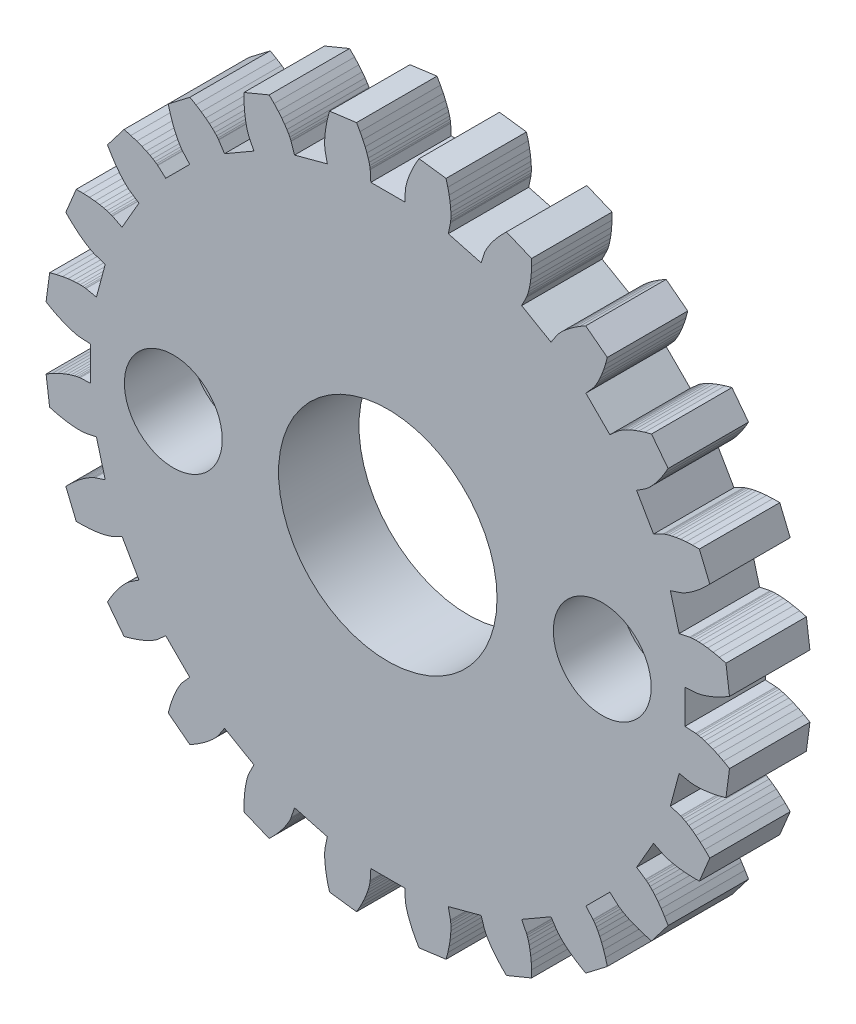
SolidWorks part; units mm, degrees
material "ABS"
ref_plane "Front Plane" through (0, 0, 0) normal (0, 0, 1) x (1, 0, 0)
ref_plane "Top Plane" through (0, 0, 0) normal (0, 1, 0) x (1, 0, 0)
ref_plane "Right Plane" through (0, 0, 0) normal (1, 0, 0) x (0, 0, -1)
sketch "Model" plane through (0, 0, 0) normal (0, 0, 1) x (1, 0, 0)
  line L0 (11.4813, -0.6559) -> (11.0819, -0.6331)
  line L1 (11.0819, -0.6331) -> (11.0819, 0.6331)
  line L2 (11.4813, 0.6559) -> (11.0819, 0.6331)
  line L3 (11.4813, 0.6559) -> (11.495, 0.6571)
  line L4 (11.495, 0.6571) -> (11.5358, 0.6626)
  line L5 (11.5358, 0.6626) -> (11.6033, 0.6749)
  line L6 (11.6033, 0.6749) -> (11.697, 0.6968)
  line L7 (11.697, 0.6968) -> (11.8158, 0.7307)
  line L8 (11.8158, 0.7307) -> (11.9589, 0.7792)
  line L9 (11.9589, 0.7792) -> (12.125, 0.8446)
  line L10 (12.125, 0.8446) -> (12.3128, 0.9294)
  line L11 (12.3128, 0.9294) -> (12.5206, 1.0358)
  line L12 (12.5206, 1.0358) -> (12.7468, 1.1658)
  line L13 (11.2598, 2.338) -> (11.2734, 2.3404)
  line L14 (11.2734, 2.3404) -> (11.3142, 2.3457)
  line L15 (11.3142, 2.3457) -> (11.3827, 2.3512)
  line L16 (11.3827, 2.3512) -> (11.4787, 2.3543)
  line L17 (11.4787, 2.3543) -> (11.6023, 2.3524)
  line L18 (11.6023, 2.3524) -> (11.7531, 2.3426)
  line L19 (11.7531, 2.3426) -> (11.9305, 2.3223)
  line L20 (11.9305, 2.3223) -> (12.1338, 2.289)
  line L21 (12.1338, 2.289) -> (12.362, 2.2401)
  line L22 (12.362, 2.2401) -> (12.6142, 2.173)
  line L23 (12.7468, 1.1658) -> (12.6142, 2.173)
  line L24 (11.2598, 2.338) -> (10.8682, 2.2567)
  line L25 (10.8682, 2.2567) -> (10.5405, 3.4797)
  line L26 (10.9203, 3.6051) -> (10.5405, 3.4797)
  line L27 (10.9203, 3.6051) -> (10.9332, 3.6098)
  line L28 (10.9332, 3.6098) -> (10.9712, 3.6257)
  line L29 (10.9712, 3.6257) -> (11.0333, 3.6551)
  line L30 (11.0333, 3.6551) -> (11.1181, 3.7004)
  line L31 (11.1181, 3.7004) -> (11.2241, 3.764)
  line L32 (11.2241, 3.764) -> (11.3497, 3.8478)
  line L33 (11.3497, 3.8478) -> (11.4933, 3.954)
  line L34 (11.4933, 3.954) -> (11.6527, 4.0845)
  line L35 (11.6527, 4.0845) -> (11.8259, 4.241)
  line L36 (11.8259, 4.241) -> (12.0107, 4.4252)
  line L37 (10.271, 5.1726) -> (10.2835, 5.1784)
  line L38 (10.2835, 5.1784) -> (10.3216, 5.1941)
  line L39 (10.3216, 5.1941) -> (10.3863, 5.2172)
  line L40 (10.3863, 5.2172) -> (10.4783, 5.245)
  line L41 (10.4783, 5.245) -> (10.5981, 5.2751)
  line L42 (10.5981, 5.2751) -> (10.7463, 5.3047)
  line L43 (10.7463, 5.3047) -> (10.9229, 5.331)
  line L44 (10.9229, 5.331) -> (11.1279, 5.3515)
  line L45 (11.1279, 5.3515) -> (11.361, 5.3633)
  line L46 (11.361, 5.3633) -> (11.622, 5.3638)
  line L47 (12.0107, 4.4252) -> (11.622, 5.3638)
  line L48 (10.271, 5.1726) -> (9.9138, 4.9927)
  line L49 (9.9138, 4.9927) -> (9.2807, 6.0892)
  line L50 (9.6151, 6.3087) -> (9.2807, 6.0892)
  line L51 (9.6151, 6.3087) -> (9.6264, 6.3166)
  line L52 (9.6264, 6.3166) -> (9.659, 6.3417)
  line L53 (9.659, 6.3417) -> (9.7113, 6.3862)
  line L54 (9.7113, 6.3862) -> (9.7815, 6.4519)
  line L55 (9.7815, 6.4519) -> (9.8675, 6.5407)
  line L56 (9.8675, 6.5407) -> (9.9671, 6.6542)
  line L57 (9.9671, 6.6542) -> (10.0783, 6.794)
  line L58 (10.0783, 6.794) -> (10.1985, 6.9613)
  line L59 (10.1985, 6.9613) -> (10.3253, 7.1573)
  line L60 (10.3253, 7.1573) -> (10.4561, 7.383)
  line L61 (8.5823, 7.6547) -> (8.5928, 7.6635)
  line L62 (8.5928, 7.6635) -> (8.6256, 7.6885)
  line L63 (8.6256, 7.6885) -> (8.6821, 7.7275)
  line L64 (8.6821, 7.7275) -> (8.7637, 7.7783)
  line L65 (8.7637, 7.7783) -> (8.8717, 7.8384)
  line L66 (8.8717, 7.8384) -> (9.0072, 7.9053)
  line L67 (9.0072, 7.9053) -> (9.1709, 7.9764)
  line L68 (9.1709, 7.9764) -> (9.3636, 8.0492)
  line L69 (9.3636, 8.0492) -> (9.5858, 8.121)
  line L70 (9.5858, 8.121) -> (9.8377, 8.189)
  line L71 (10.4561, 7.383) -> (9.8377, 8.189)
  line L72 (8.5823, 7.6547) -> (8.2838, 7.3885)
  line L73 (8.2838, 7.3885) -> (7.3885, 8.2838)
  line L74 (7.6547, 8.5823) -> (7.3885, 8.2838)
  line L75 (7.6547, 8.5823) -> (7.6635, 8.5928)
  line L76 (7.6635, 8.5928) -> (7.6885, 8.6256)
  line L77 (7.6885, 8.6256) -> (7.7275, 8.6821)
  line L78 (7.7275, 8.6821) -> (7.7783, 8.7637)
  line L79 (7.7783, 8.7637) -> (7.8384, 8.8717)
  line L80 (7.8384, 8.8717) -> (7.9053, 9.0072)
  line L81 (7.9053, 9.0072) -> (7.9764, 9.1709)
  line L82 (7.9764, 9.1709) -> (8.0492, 9.3636)
  line L83 (8.0492, 9.3636) -> (8.121, 9.5858)
  line L84 (8.121, 9.5858) -> (8.189, 9.8377)
  line L85 (6.3087, 9.6151) -> (6.3166, 9.6264)
  line L86 (6.3166, 9.6264) -> (6.3417, 9.659)
  line L87 (6.3417, 9.659) -> (6.3862, 9.7113)
  line L88 (6.3862, 9.7113) -> (6.4519, 9.7815)
  line L89 (6.4519, 9.7815) -> (6.5407, 9.8675)
  line L90 (6.5407, 9.8675) -> (6.6542, 9.9671)
  line L91 (6.6542, 9.9671) -> (6.794, 10.0783)
  line L92 (6.794, 10.0783) -> (6.9613, 10.1985)
  line L93 (6.9613, 10.1985) -> (7.1573, 10.3253)
  line L94 (7.1573, 10.3253) -> (7.383, 10.4561)
  line L95 (8.189, 9.8377) -> (7.383, 10.4561)
  line L96 (6.3087, 9.6151) -> (6.0892, 9.2807)
  line L97 (6.0892, 9.2807) -> (4.9927, 9.9138)
  line L98 (5.1726, 10.271) -> (4.9927, 9.9138)
  line L99 (5.1726, 10.271) -> (5.1784, 10.2835)
  line L100 (5.1784, 10.2835) -> (5.1941, 10.3216)
  line L101 (5.1941, 10.3216) -> (5.2172, 10.3863)
  line L102 (5.2172, 10.3863) -> (5.245, 10.4783)
  line L103 (5.245, 10.4783) -> (5.2751, 10.5981)
  line L104 (5.2751, 10.5981) -> (5.3047, 10.7463)
  line L105 (5.3047, 10.7463) -> (5.331, 10.9229)
  line L106 (5.331, 10.9229) -> (5.3515, 11.1279)
  line L107 (5.3515, 11.1279) -> (5.3633, 11.361)
  line L108 (5.3633, 11.361) -> (5.3638, 11.622)
  line L109 (3.6051, 10.9203) -> (3.6098, 10.9332)
  line L110 (3.6098, 10.9332) -> (3.6257, 10.9712)
  line L111 (3.6257, 10.9712) -> (3.6551, 11.0333)
  line L112 (3.6551, 11.0333) -> (3.7004, 11.1181)
  line L113 (3.7004, 11.1181) -> (3.764, 11.2241)
  line L114 (3.764, 11.2241) -> (3.8478, 11.3497)
  line L115 (3.8478, 11.3497) -> (3.954, 11.4933)
  line L116 (3.954, 11.4933) -> (4.0845, 11.6527)
  line L117 (4.0845, 11.6527) -> (4.241, 11.8259)
  line L118 (4.241, 11.8259) -> (4.4252, 12.0107)
  line L119 (5.3638, 11.622) -> (4.4252, 12.0107)
  line L120 (3.6051, 10.9203) -> (3.4797, 10.5405)
  line L121 (3.4797, 10.5405) -> (2.2567, 10.8682)
  line L122 (2.338, 11.2598) -> (2.2567, 10.8682)
  line L123 (2.338, 11.2598) -> (2.3404, 11.2734)
  line L124 (2.3404, 11.2734) -> (2.3457, 11.3142)
  line L125 (2.3457, 11.3142) -> (2.3512, 11.3827)
  line L126 (2.3512, 11.3827) -> (2.3543, 11.4787)
  line L127 (2.3543, 11.4787) -> (2.3524, 11.6023)
  line L128 (2.3524, 11.6023) -> (2.3426, 11.7531)
  line L129 (2.3426, 11.7531) -> (2.3223, 11.9305)
  line L130 (2.3223, 11.9305) -> (2.289, 12.1338)
  line L131 (2.289, 12.1338) -> (2.2401, 12.362)
  line L132 (2.2401, 12.362) -> (2.173, 12.6142)
  line L133 (0.6559, 11.4813) -> (0.6571, 11.495)
  line L134 (0.6571, 11.495) -> (0.6626, 11.5358)
  line L135 (0.6626, 11.5358) -> (0.6749, 11.6033)
  line L136 (0.6749, 11.6033) -> (0.6968, 11.697)
  line L137 (0.6968, 11.697) -> (0.7307, 11.8158)
  line L138 (0.7307, 11.8158) -> (0.7792, 11.9589)
  line L139 (0.7792, 11.9589) -> (0.8446, 12.125)
  line L140 (0.8446, 12.125) -> (0.9294, 12.3128)
  line L141 (0.9294, 12.3128) -> (1.0358, 12.5206)
  line L142 (1.0358, 12.5206) -> (1.1658, 12.7468)
  line L143 (2.173, 12.6142) -> (1.1658, 12.7468)
  line L144 (0.6559, 11.4813) -> (0.6331, 11.0819)
  line L145 (0.6331, 11.0819) -> (-0.6331, 11.0819)
  line L146 (-0.6559, 11.4813) -> (-0.6331, 11.0819)
  line L147 (-0.6559, 11.4813) -> (-0.6571, 11.495)
  line L148 (-0.6571, 11.495) -> (-0.6626, 11.5358)
  line L149 (-0.6626, 11.5358) -> (-0.6749, 11.6033)
  line L150 (-0.6749, 11.6033) -> (-0.6968, 11.697)
  line L151 (-0.6968, 11.697) -> (-0.7307, 11.8158)
  line L152 (-0.7307, 11.8158) -> (-0.7792, 11.9589)
  line L153 (-0.7792, 11.9589) -> (-0.8446, 12.125)
  line L154 (-0.8446, 12.125) -> (-0.9294, 12.3128)
  line L155 (-0.9294, 12.3128) -> (-1.0358, 12.5206)
  line L156 (-1.0358, 12.5206) -> (-1.1658, 12.7468)
  line L157 (-2.338, 11.2598) -> (-2.3404, 11.2734)
  line L158 (-2.3404, 11.2734) -> (-2.3457, 11.3142)
  line L159 (-2.3457, 11.3142) -> (-2.3512, 11.3827)
  line L160 (-2.3512, 11.3827) -> (-2.3543, 11.4787)
  line L161 (-2.3543, 11.4787) -> (-2.3524, 11.6023)
  line L162 (-2.3524, 11.6023) -> (-2.3426, 11.7531)
  line L163 (-2.3426, 11.7531) -> (-2.3223, 11.9305)
  line L164 (-2.3223, 11.9305) -> (-2.289, 12.1338)
  line L165 (-2.289, 12.1338) -> (-2.2401, 12.362)
  line L166 (-2.2401, 12.362) -> (-2.173, 12.6142)
  line L167 (-1.1658, 12.7468) -> (-2.173, 12.6142)
  line L168 (-2.338, 11.2598) -> (-2.2567, 10.8682)
  line L169 (-2.2567, 10.8682) -> (-3.4797, 10.5405)
  line L170 (-3.6051, 10.9203) -> (-3.4797, 10.5405)
  line L171 (-3.6051, 10.9203) -> (-3.6098, 10.9332)
  line L172 (-3.6098, 10.9332) -> (-3.6257, 10.9712)
  line L173 (-3.6257, 10.9712) -> (-3.6551, 11.0333)
  line L174 (-3.6551, 11.0333) -> (-3.7004, 11.1181)
  line L175 (-3.7004, 11.1181) -> (-3.764, 11.2241)
  line L176 (-3.764, 11.2241) -> (-3.8478, 11.3497)
  line L177 (-3.8478, 11.3497) -> (-3.954, 11.4933)
  line L178 (-3.954, 11.4933) -> (-4.0845, 11.6527)
  line L179 (-4.0845, 11.6527) -> (-4.241, 11.8259)
  line L180 (-4.241, 11.8259) -> (-4.4252, 12.0107)
  line L181 (-5.1726, 10.271) -> (-5.1784, 10.2835)
  line L182 (-5.1784, 10.2835) -> (-5.1941, 10.3216)
  line L183 (-5.1941, 10.3216) -> (-5.2172, 10.3863)
  line L184 (-5.2172, 10.3863) -> (-5.245, 10.4783)
  line L185 (-5.245, 10.4783) -> (-5.2751, 10.5981)
  line L186 (-5.2751, 10.5981) -> (-5.3047, 10.7463)
  line L187 (-5.3047, 10.7463) -> (-5.331, 10.9229)
  line L188 (-5.331, 10.9229) -> (-5.3515, 11.1279)
  line L189 (-5.3515, 11.1279) -> (-5.3633, 11.361)
  line L190 (-5.3633, 11.361) -> (-5.3638, 11.622)
  line L191 (-4.4252, 12.0107) -> (-5.3638, 11.622)
  line L192 (-5.1726, 10.271) -> (-4.9927, 9.9138)
  line L193 (-4.9927, 9.9138) -> (-6.0892, 9.2807)
  line L194 (-6.3087, 9.6151) -> (-6.0892, 9.2807)
  line L195 (-6.3087, 9.6151) -> (-6.3166, 9.6264)
  line L196 (-6.3166, 9.6264) -> (-6.3417, 9.659)
  line L197 (-6.3417, 9.659) -> (-6.3862, 9.7113)
  line L198 (-6.3862, 9.7113) -> (-6.4519, 9.7815)
  line L199 (-6.4519, 9.7815) -> (-6.5407, 9.8675)
  line L200 (-6.5407, 9.8675) -> (-6.6542, 9.9671)
  line L201 (-6.6542, 9.9671) -> (-6.794, 10.0783)
  line L202 (-6.794, 10.0783) -> (-6.9613, 10.1985)
  line L203 (-6.9613, 10.1985) -> (-7.1573, 10.3253)
  line L204 (-7.1573, 10.3253) -> (-7.383, 10.4561)
  line L205 (-7.6547, 8.5823) -> (-7.6635, 8.5928)
  line L206 (-7.6635, 8.5928) -> (-7.6885, 8.6256)
  line L207 (-7.6885, 8.6256) -> (-7.7275, 8.6821)
  line L208 (-7.7275, 8.6821) -> (-7.7783, 8.7637)
  line L209 (-7.7783, 8.7637) -> (-7.8384, 8.8717)
  line L210 (-7.8384, 8.8717) -> (-7.9053, 9.0072)
  line L211 (-7.9053, 9.0072) -> (-7.9764, 9.1709)
  line L212 (-7.9764, 9.1709) -> (-8.0492, 9.3636)
  line L213 (-8.0492, 9.3636) -> (-8.121, 9.5858)
  line L214 (-8.121, 9.5858) -> (-8.189, 9.8377)
  line L215 (-7.383, 10.4561) -> (-8.189, 9.8377)
  line L216 (-7.6547, 8.5823) -> (-7.3885, 8.2838)
  line L217 (-7.3885, 8.2838) -> (-8.2838, 7.3885)
  line L218 (-8.5823, 7.6547) -> (-8.2838, 7.3885)
  line L219 (-8.5823, 7.6547) -> (-8.5928, 7.6635)
  line L220 (-8.5928, 7.6635) -> (-8.6256, 7.6885)
  line L221 (-8.6256, 7.6885) -> (-8.6821, 7.7275)
  line L222 (-8.6821, 7.7275) -> (-8.7637, 7.7783)
  line L223 (-8.7637, 7.7783) -> (-8.8717, 7.8384)
  line L224 (-8.8717, 7.8384) -> (-9.0072, 7.9053)
  line L225 (-9.0072, 7.9053) -> (-9.1709, 7.9764)
  line L226 (-9.1709, 7.9764) -> (-9.3636, 8.0492)
  line L227 (-9.3636, 8.0492) -> (-9.5858, 8.121)
  line L228 (-9.5858, 8.121) -> (-9.8377, 8.189)
  line L229 (-9.6151, 6.3087) -> (-9.6264, 6.3166)
  line L230 (-9.6264, 6.3166) -> (-9.659, 6.3417)
  line L231 (-9.659, 6.3417) -> (-9.7113, 6.3862)
  line L232 (-9.7113, 6.3862) -> (-9.7815, 6.4519)
  line L233 (-9.7815, 6.4519) -> (-9.8675, 6.5407)
  line L234 (-9.8675, 6.5407) -> (-9.9671, 6.6542)
  line L235 (-9.9671, 6.6542) -> (-10.0783, 6.794)
  line L236 (-10.0783, 6.794) -> (-10.1985, 6.9613)
  line L237 (-10.1985, 6.9613) -> (-10.3253, 7.1573)
  line L238 (-10.3253, 7.1573) -> (-10.4561, 7.383)
  line L239 (-9.8377, 8.189) -> (-10.4561, 7.383)
  line L240 (-9.6151, 6.3087) -> (-9.2807, 6.0892)
  line L241 (-9.2807, 6.0892) -> (-9.9138, 4.9927)
  line L242 (-10.271, 5.1726) -> (-9.9138, 4.9927)
  line L243 (-10.271, 5.1726) -> (-10.2835, 5.1784)
  line L244 (-10.2835, 5.1784) -> (-10.3216, 5.1941)
  line L245 (-10.3216, 5.1941) -> (-10.3863, 5.2172)
  line L246 (-10.3863, 5.2172) -> (-10.4783, 5.245)
  line L247 (-10.4783, 5.245) -> (-10.5981, 5.2751)
  line L248 (-10.5981, 5.2751) -> (-10.7463, 5.3047)
  line L249 (-10.7463, 5.3047) -> (-10.9229, 5.331)
  line L250 (-10.9229, 5.331) -> (-11.1279, 5.3515)
  line L251 (-11.1279, 5.3515) -> (-11.361, 5.3633)
  line L252 (-11.361, 5.3633) -> (-11.622, 5.3638)
  line L253 (-10.9203, 3.6051) -> (-10.9332, 3.6098)
  line L254 (-10.9332, 3.6098) -> (-10.9712, 3.6257)
  line L255 (-10.9712, 3.6257) -> (-11.0333, 3.6551)
  line L256 (-11.0333, 3.6551) -> (-11.1181, 3.7004)
  line L257 (-11.1181, 3.7004) -> (-11.2241, 3.764)
  line L258 (-11.2241, 3.764) -> (-11.3497, 3.8478)
  line L259 (-11.3497, 3.8478) -> (-11.4933, 3.954)
  line L260 (-11.4933, 3.954) -> (-11.6527, 4.0845)
  line L261 (-11.6527, 4.0845) -> (-11.8259, 4.241)
  line L262 (-11.8259, 4.241) -> (-12.0107, 4.4252)
  line L263 (-11.622, 5.3638) -> (-12.0107, 4.4252)
  line L264 (-10.9203, 3.6051) -> (-10.5405, 3.4797)
  line L265 (-10.5405, 3.4797) -> (-10.8682, 2.2567)
  line L266 (-11.2598, 2.338) -> (-10.8682, 2.2567)
  line L267 (-11.2598, 2.338) -> (-11.2734, 2.3404)
  line L268 (-11.2734, 2.3404) -> (-11.3142, 2.3457)
  line L269 (-11.3142, 2.3457) -> (-11.3827, 2.3512)
  line L270 (-11.3827, 2.3512) -> (-11.4787, 2.3543)
  line L271 (-11.4787, 2.3543) -> (-11.6023, 2.3524)
  line L272 (-11.6023, 2.3524) -> (-11.7531, 2.3426)
  line L273 (-11.7531, 2.3426) -> (-11.9305, 2.3223)
  line L274 (-11.9305, 2.3223) -> (-12.1338, 2.289)
  line L275 (-12.1338, 2.289) -> (-12.362, 2.2401)
  line L276 (-12.362, 2.2401) -> (-12.6142, 2.173)
  line L277 (-11.4813, 0.6559) -> (-11.495, 0.6571)
  line L278 (-11.495, 0.6571) -> (-11.5358, 0.6626)
  line L279 (-11.5358, 0.6626) -> (-11.6033, 0.6749)
  line L280 (-11.6033, 0.6749) -> (-11.697, 0.6968)
  line L281 (-11.697, 0.6968) -> (-11.8158, 0.7307)
  line L282 (-11.8158, 0.7307) -> (-11.9589, 0.7792)
  line L283 (-11.9589, 0.7792) -> (-12.125, 0.8446)
  line L284 (-12.125, 0.8446) -> (-12.3128, 0.9294)
  line L285 (-12.3128, 0.9294) -> (-12.5206, 1.0358)
  line L286 (-12.5206, 1.0358) -> (-12.7468, 1.1658)
  line L287 (-12.6142, 2.173) -> (-12.7468, 1.1658)
  line L288 (-11.4813, 0.6559) -> (-11.0819, 0.6331)
  line L289 (-11.0819, 0.6331) -> (-11.0819, -0.6331)
  line L290 (-11.4813, -0.6559) -> (-11.0819, -0.6331)
  line L291 (-11.4813, -0.6559) -> (-11.495, -0.6571)
  line L292 (-11.495, -0.6571) -> (-11.5358, -0.6626)
  line L293 (-11.5358, -0.6626) -> (-11.6033, -0.6749)
  line L294 (-11.6033, -0.6749) -> (-11.697, -0.6968)
  line L295 (-11.697, -0.6968) -> (-11.8158, -0.7307)
  line L296 (-11.8158, -0.7307) -> (-11.9589, -0.7792)
  line L297 (-11.9589, -0.7792) -> (-12.125, -0.8446)
  line L298 (-12.125, -0.8446) -> (-12.3128, -0.9294)
  line L299 (-12.3128, -0.9294) -> (-12.5206, -1.0358)
  line L300 (-12.5206, -1.0358) -> (-12.7468, -1.1658)
  line L301 (-11.2598, -2.338) -> (-11.2734, -2.3404)
  line L302 (-11.2734, -2.3404) -> (-11.3142, -2.3457)
  line L303 (-11.3142, -2.3457) -> (-11.3827, -2.3512)
  line L304 (-11.3827, -2.3512) -> (-11.4787, -2.3543)
  line L305 (-11.4787, -2.3543) -> (-11.6023, -2.3524)
  line L306 (-11.6023, -2.3524) -> (-11.7531, -2.3426)
  line L307 (-11.7531, -2.3426) -> (-11.9305, -2.3223)
  line L308 (-11.9305, -2.3223) -> (-12.1338, -2.289)
  line L309 (-12.1338, -2.289) -> (-12.362, -2.2401)
  line L310 (-12.362, -2.2401) -> (-12.6142, -2.173)
  line L311 (-12.7468, -1.1658) -> (-12.6142, -2.173)
  line L312 (-11.2598, -2.338) -> (-10.8682, -2.2567)
  line L313 (-10.8682, -2.2567) -> (-10.5405, -3.4797)
  line L314 (-10.9203, -3.6051) -> (-10.5405, -3.4797)
  line L315 (-10.9203, -3.6051) -> (-10.9332, -3.6098)
  line L316 (-10.9332, -3.6098) -> (-10.9712, -3.6257)
  line L317 (-10.9712, -3.6257) -> (-11.0333, -3.6551)
  line L318 (-11.0333, -3.6551) -> (-11.1181, -3.7004)
  line L319 (-11.1181, -3.7004) -> (-11.2241, -3.764)
  line L320 (-11.2241, -3.764) -> (-11.3497, -3.8478)
  line L321 (-11.3497, -3.8478) -> (-11.4933, -3.954)
  line L322 (-11.4933, -3.954) -> (-11.6527, -4.0845)
  line L323 (-11.6527, -4.0845) -> (-11.8259, -4.241)
  line L324 (-11.8259, -4.241) -> (-12.0107, -4.4252)
  line L325 (-10.271, -5.1726) -> (-10.2835, -5.1784)
  line L326 (-10.2835, -5.1784) -> (-10.3216, -5.1941)
  line L327 (-10.3216, -5.1941) -> (-10.3863, -5.2172)
  line L328 (-10.3863, -5.2172) -> (-10.4783, -5.245)
  line L329 (-10.4783, -5.245) -> (-10.5981, -5.2751)
  line L330 (-10.5981, -5.2751) -> (-10.7463, -5.3047)
  line L331 (-10.7463, -5.3047) -> (-10.9229, -5.331)
  line L332 (-10.9229, -5.331) -> (-11.1279, -5.3515)
  line L333 (-11.1279, -5.3515) -> (-11.361, -5.3633)
  line L334 (-11.361, -5.3633) -> (-11.622, -5.3638)
  line L335 (-12.0107, -4.4252) -> (-11.622, -5.3638)
  line L336 (-10.271, -5.1726) -> (-9.9138, -4.9927)
  line L337 (-9.9138, -4.9927) -> (-9.2807, -6.0892)
  line L338 (-9.6151, -6.3087) -> (-9.2807, -6.0892)
  line L339 (-9.6151, -6.3087) -> (-9.6264, -6.3166)
  line L340 (-9.6264, -6.3166) -> (-9.659, -6.3417)
  line L341 (-9.659, -6.3417) -> (-9.7113, -6.3862)
  line L342 (-9.7113, -6.3862) -> (-9.7815, -6.4519)
  line L343 (-9.7815, -6.4519) -> (-9.8675, -6.5407)
  line L344 (-9.8675, -6.5407) -> (-9.9671, -6.6542)
  line L345 (-9.9671, -6.6542) -> (-10.0783, -6.794)
  line L346 (-10.0783, -6.794) -> (-10.1985, -6.9613)
  line L347 (-10.1985, -6.9613) -> (-10.3253, -7.1573)
  line L348 (-10.3253, -7.1573) -> (-10.4561, -7.383)
  line L349 (-8.5823, -7.6547) -> (-8.5928, -7.6635)
  line L350 (-8.5928, -7.6635) -> (-8.6256, -7.6885)
  line L351 (-8.6256, -7.6885) -> (-8.6821, -7.7275)
  line L352 (-8.6821, -7.7275) -> (-8.7637, -7.7783)
  line L353 (-8.7637, -7.7783) -> (-8.8717, -7.8384)
  line L354 (-8.8717, -7.8384) -> (-9.0072, -7.9053)
  line L355 (-9.0072, -7.9053) -> (-9.1709, -7.9764)
  line L356 (-9.1709, -7.9764) -> (-9.3636, -8.0492)
  line L357 (-9.3636, -8.0492) -> (-9.5858, -8.121)
  line L358 (-9.5858, -8.121) -> (-9.8377, -8.189)
  line L359 (-10.4561, -7.383) -> (-9.8377, -8.189)
  line L360 (-8.5823, -7.6547) -> (-8.2838, -7.3885)
  line L361 (-8.2838, -7.3885) -> (-7.3885, -8.2838)
  line L362 (-7.6547, -8.5823) -> (-7.3885, -8.2838)
  line L363 (-7.6547, -8.5823) -> (-7.6635, -8.5928)
  line L364 (-7.6635, -8.5928) -> (-7.6885, -8.6256)
  line L365 (-7.6885, -8.6256) -> (-7.7275, -8.6821)
  line L366 (-7.7275, -8.6821) -> (-7.7783, -8.7637)
  line L367 (-7.7783, -8.7637) -> (-7.8384, -8.8717)
  line L368 (-7.8384, -8.8717) -> (-7.9053, -9.0072)
  line L369 (-7.9053, -9.0072) -> (-7.9764, -9.1709)
  line L370 (-7.9764, -9.1709) -> (-8.0492, -9.3636)
  line L371 (-8.0492, -9.3636) -> (-8.121, -9.5858)
  line L372 (-8.121, -9.5858) -> (-8.189, -9.8377)
  line L373 (-6.3087, -9.6151) -> (-6.3166, -9.6264)
  line L374 (-6.3166, -9.6264) -> (-6.3417, -9.659)
  line L375 (-6.3417, -9.659) -> (-6.3862, -9.7113)
  line L376 (-6.3862, -9.7113) -> (-6.4519, -9.7815)
  line L377 (-6.4519, -9.7815) -> (-6.5407, -9.8675)
  line L378 (-6.5407, -9.8675) -> (-6.6542, -9.9671)
  line L379 (-6.6542, -9.9671) -> (-6.794, -10.0783)
  line L380 (-6.794, -10.0783) -> (-6.9613, -10.1985)
  line L381 (-6.9613, -10.1985) -> (-7.1573, -10.3253)
  line L382 (-7.1573, -10.3253) -> (-7.383, -10.4561)
  line L383 (-8.189, -9.8377) -> (-7.383, -10.4561)
  line L384 (-6.3087, -9.6151) -> (-6.0892, -9.2807)
  line L385 (-6.0892, -9.2807) -> (-4.9927, -9.9138)
  line L386 (-5.1726, -10.271) -> (-4.9927, -9.9138)
  line L387 (-5.1726, -10.271) -> (-5.1784, -10.2835)
  line L388 (-5.1784, -10.2835) -> (-5.1941, -10.3216)
  line L389 (-5.1941, -10.3216) -> (-5.2172, -10.3863)
  line L390 (-5.2172, -10.3863) -> (-5.245, -10.4783)
  line L391 (-5.245, -10.4783) -> (-5.2751, -10.5981)
  line L392 (-5.2751, -10.5981) -> (-5.3047, -10.7463)
  line L393 (-5.3047, -10.7463) -> (-5.331, -10.9229)
  line L394 (-5.331, -10.9229) -> (-5.3515, -11.1279)
  line L395 (-5.3515, -11.1279) -> (-5.3633, -11.361)
  line L396 (-5.3633, -11.361) -> (-5.3638, -11.622)
  line L397 (-3.6051, -10.9203) -> (-3.6098, -10.9332)
  line L398 (-3.6098, -10.9332) -> (-3.6257, -10.9712)
  line L399 (-3.6257, -10.9712) -> (-3.6551, -11.0333)
  line L400 (-3.6551, -11.0333) -> (-3.7004, -11.1181)
  line L401 (-3.7004, -11.1181) -> (-3.764, -11.2241)
  line L402 (-3.764, -11.2241) -> (-3.8478, -11.3497)
  line L403 (-3.8478, -11.3497) -> (-3.954, -11.4933)
  line L404 (-3.954, -11.4933) -> (-4.0845, -11.6527)
  line L405 (-4.0845, -11.6527) -> (-4.241, -11.8259)
  line L406 (-4.241, -11.8259) -> (-4.4252, -12.0107)
  line L407 (-5.3638, -11.622) -> (-4.4252, -12.0107)
  line L408 (-3.6051, -10.9203) -> (-3.4797, -10.5405)
  line L409 (-3.4797, -10.5405) -> (-2.2567, -10.8682)
  line L410 (-2.338, -11.2598) -> (-2.2567, -10.8682)
  line L411 (-2.338, -11.2598) -> (-2.3404, -11.2734)
  line L412 (-2.3404, -11.2734) -> (-2.3457, -11.3142)
  line L413 (-2.3457, -11.3142) -> (-2.3512, -11.3827)
  line L414 (-2.3512, -11.3827) -> (-2.3543, -11.4787)
  line L415 (-2.3543, -11.4787) -> (-2.3524, -11.6023)
  line L416 (-2.3524, -11.6023) -> (-2.3426, -11.7531)
  line L417 (-2.3426, -11.7531) -> (-2.3223, -11.9305)
  line L418 (-2.3223, -11.9305) -> (-2.289, -12.1338)
  line L419 (-2.289, -12.1338) -> (-2.2401, -12.362)
  line L420 (-2.2401, -12.362) -> (-2.173, -12.6142)
  line L421 (-0.6559, -11.4813) -> (-0.6571, -11.495)
  line L422 (-0.6571, -11.495) -> (-0.6626, -11.5358)
  line L423 (-0.6626, -11.5358) -> (-0.6749, -11.6033)
  line L424 (-0.6749, -11.6033) -> (-0.6968, -11.697)
  line L425 (-0.6968, -11.697) -> (-0.7307, -11.8158)
  line L426 (-0.7307, -11.8158) -> (-0.7792, -11.9589)
  line L427 (-0.7792, -11.9589) -> (-0.8446, -12.125)
  line L428 (-0.8446, -12.125) -> (-0.9294, -12.3128)
  line L429 (-0.9294, -12.3128) -> (-1.0358, -12.5206)
  line L430 (-1.0358, -12.5206) -> (-1.1658, -12.7468)
  line L431 (-2.173, -12.6142) -> (-1.1658, -12.7468)
  line L432 (-0.6559, -11.4813) -> (-0.6331, -11.0819)
  line L433 (-0.6331, -11.0819) -> (0.6331, -11.0819)
  line L434 (0.6559, -11.4813) -> (0.6331, -11.0819)
  line L435 (0.6559, -11.4813) -> (0.6571, -11.495)
  line L436 (0.6571, -11.495) -> (0.6626, -11.5358)
  line L437 (0.6626, -11.5358) -> (0.6749, -11.6033)
  line L438 (0.6749, -11.6033) -> (0.6968, -11.697)
  line L439 (0.6968, -11.697) -> (0.7307, -11.8158)
  line L440 (0.7307, -11.8158) -> (0.7792, -11.9589)
  line L441 (0.7792, -11.9589) -> (0.8446, -12.125)
  line L442 (0.8446, -12.125) -> (0.9294, -12.3128)
  line L443 (0.9294, -12.3128) -> (1.0358, -12.5206)
  line L444 (1.0358, -12.5206) -> (1.1658, -12.7468)
  line L445 (2.338, -11.2598) -> (2.3404, -11.2734)
  line L446 (2.3404, -11.2734) -> (2.3457, -11.3142)
  line L447 (2.3457, -11.3142) -> (2.3512, -11.3827)
  line L448 (2.3512, -11.3827) -> (2.3543, -11.4787)
  line L449 (2.3543, -11.4787) -> (2.3524, -11.6023)
  line L450 (2.3524, -11.6023) -> (2.3426, -11.7531)
  line L451 (2.3426, -11.7531) -> (2.3223, -11.9305)
  line L452 (2.3223, -11.9305) -> (2.289, -12.1338)
  line L453 (2.289, -12.1338) -> (2.2401, -12.362)
  line L454 (2.2401, -12.362) -> (2.173, -12.6142)
  line L455 (1.1658, -12.7468) -> (2.173, -12.6142)
  line L456 (2.338, -11.2598) -> (2.2567, -10.8682)
  line L457 (2.2567, -10.8682) -> (3.4797, -10.5405)
  line L458 (3.6051, -10.9203) -> (3.4797, -10.5405)
  line L459 (3.6051, -10.9203) -> (3.6098, -10.9332)
  line L460 (3.6098, -10.9332) -> (3.6257, -10.9712)
  line L461 (3.6257, -10.9712) -> (3.6551, -11.0333)
  line L462 (3.6551, -11.0333) -> (3.7004, -11.1181)
  line L463 (3.7004, -11.1181) -> (3.764, -11.2241)
  line L464 (3.764, -11.2241) -> (3.8478, -11.3497)
  line L465 (3.8478, -11.3497) -> (3.954, -11.4933)
  line L466 (3.954, -11.4933) -> (4.0845, -11.6527)
  line L467 (4.0845, -11.6527) -> (4.241, -11.8259)
  line L468 (4.241, -11.8259) -> (4.4252, -12.0107)
  line L469 (5.1726, -10.271) -> (5.1784, -10.2835)
  line L470 (5.1784, -10.2835) -> (5.1941, -10.3216)
  line L471 (5.1941, -10.3216) -> (5.2172, -10.3863)
  line L472 (5.2172, -10.3863) -> (5.245, -10.4783)
  line L473 (5.245, -10.4783) -> (5.2751, -10.5981)
  line L474 (5.2751, -10.5981) -> (5.3047, -10.7463)
  line L475 (5.3047, -10.7463) -> (5.331, -10.9229)
  line L476 (5.331, -10.9229) -> (5.3515, -11.1279)
  line L477 (5.3515, -11.1279) -> (5.3633, -11.361)
  line L478 (5.3633, -11.361) -> (5.3638, -11.622)
  line L479 (4.4252, -12.0107) -> (5.3638, -11.622)
  line L480 (5.1726, -10.271) -> (4.9927, -9.9138)
  line L481 (4.9927, -9.9138) -> (6.0892, -9.2807)
  line L482 (6.3087, -9.6151) -> (6.0892, -9.2807)
  line L483 (6.3087, -9.6151) -> (6.3166, -9.6264)
  line L484 (6.3166, -9.6264) -> (6.3417, -9.659)
  line L485 (6.3417, -9.659) -> (6.3862, -9.7113)
  line L486 (6.3862, -9.7113) -> (6.4519, -9.7815)
  line L487 (6.4519, -9.7815) -> (6.5407, -9.8675)
  line L488 (6.5407, -9.8675) -> (6.6542, -9.9671)
  line L489 (6.6542, -9.9671) -> (6.794, -10.0783)
  line L490 (6.794, -10.0783) -> (6.9613, -10.1985)
  line L491 (6.9613, -10.1985) -> (7.1573, -10.3253)
  line L492 (7.1573, -10.3253) -> (7.383, -10.4561)
  line L493 (7.6547, -8.5823) -> (7.6635, -8.5928)
  line L494 (7.6635, -8.5928) -> (7.6885, -8.6256)
  line L495 (7.6885, -8.6256) -> (7.7275, -8.6821)
  line L496 (7.7275, -8.6821) -> (7.7783, -8.7637)
  line L497 (7.7783, -8.7637) -> (7.8384, -8.8717)
  line L498 (7.8384, -8.8717) -> (7.9053, -9.0072)
  line L499 (7.9053, -9.0072) -> (7.9764, -9.1709)
  line L500 (7.9764, -9.1709) -> (8.0492, -9.3636)
  line L501 (8.0492, -9.3636) -> (8.121, -9.5858)
  line L502 (8.121, -9.5858) -> (8.189, -9.8377)
  line L503 (7.383, -10.4561) -> (8.189, -9.8377)
  line L504 (7.6547, -8.5823) -> (7.3885, -8.2838)
  line L505 (7.3885, -8.2838) -> (8.2838, -7.3885)
  line L506 (8.5823, -7.6547) -> (8.2838, -7.3885)
  line L507 (8.5823, -7.6547) -> (8.5928, -7.6635)
  line L508 (8.5928, -7.6635) -> (8.6256, -7.6885)
  line L509 (8.6256, -7.6885) -> (8.6821, -7.7275)
  line L510 (8.6821, -7.7275) -> (8.7637, -7.7783)
  line L511 (8.7637, -7.7783) -> (8.8717, -7.8384)
  line L512 (8.8717, -7.8384) -> (9.0072, -7.9053)
  line L513 (9.0072, -7.9053) -> (9.1709, -7.9764)
  line L514 (9.1709, -7.9764) -> (9.3636, -8.0492)
  line L515 (9.3636, -8.0492) -> (9.5858, -8.121)
  line L516 (9.5858, -8.121) -> (9.8377, -8.189)
  line L517 (9.6151, -6.3087) -> (9.6264, -6.3166)
  line L518 (9.6264, -6.3166) -> (9.659, -6.3417)
  line L519 (9.659, -6.3417) -> (9.7113, -6.3862)
  line L520 (9.7113, -6.3862) -> (9.7815, -6.4519)
  line L521 (9.7815, -6.4519) -> (9.8675, -6.5407)
  line L522 (9.8675, -6.5407) -> (9.9671, -6.6542)
  line L523 (9.9671, -6.6542) -> (10.0783, -6.794)
  line L524 (10.0783, -6.794) -> (10.1985, -6.9613)
  line L525 (10.1985, -6.9613) -> (10.3253, -7.1573)
  line L526 (10.3253, -7.1573) -> (10.4561, -7.383)
  line L527 (9.8377, -8.189) -> (10.4561, -7.383)
  line L528 (9.6151, -6.3087) -> (9.2807, -6.0892)
  line L529 (9.2807, -6.0892) -> (9.9138, -4.9927)
  line L530 (10.271, -5.1726) -> (9.9138, -4.9927)
  line L531 (10.271, -5.1726) -> (10.2835, -5.1784)
  line L532 (10.2835, -5.1784) -> (10.3216, -5.1941)
  line L533 (10.3216, -5.1941) -> (10.3863, -5.2172)
  line L534 (10.3863, -5.2172) -> (10.4783, -5.245)
  line L535 (10.4783, -5.245) -> (10.5981, -5.2751)
  line L536 (10.5981, -5.2751) -> (10.7463, -5.3047)
  line L537 (10.7463, -5.3047) -> (10.9229, -5.331)
  line L538 (10.9229, -5.331) -> (11.1279, -5.3515)
  line L539 (11.1279, -5.3515) -> (11.361, -5.3633)
  line L540 (11.361, -5.3633) -> (11.622, -5.3638)
  line L541 (10.9203, -3.6051) -> (10.9332, -3.6098)
  line L542 (10.9332, -3.6098) -> (10.9712, -3.6257)
  line L543 (10.9712, -3.6257) -> (11.0333, -3.6551)
  line L544 (11.0333, -3.6551) -> (11.1181, -3.7004)
  line L545 (11.1181, -3.7004) -> (11.2241, -3.764)
  line L546 (11.2241, -3.764) -> (11.3497, -3.8478)
  line L547 (11.3497, -3.8478) -> (11.4933, -3.954)
  line L548 (11.4933, -3.954) -> (11.6527, -4.0845)
  line L549 (11.6527, -4.0845) -> (11.8259, -4.241)
  line L550 (11.8259, -4.241) -> (12.0107, -4.4252)
  line L551 (11.622, -5.3638) -> (12.0107, -4.4252)
  line L552 (10.9203, -3.6051) -> (10.5405, -3.4797)
  line L553 (10.5405, -3.4797) -> (10.8682, -2.2567)
  line L554 (11.2598, -2.338) -> (10.8682, -2.2567)
  line L555 (11.2598, -2.338) -> (11.2734, -2.3404)
  line L556 (11.2734, -2.3404) -> (11.3142, -2.3457)
  line L557 (11.3142, -2.3457) -> (11.3827, -2.3512)
  line L558 (11.3827, -2.3512) -> (11.4787, -2.3543)
  line L559 (11.4787, -2.3543) -> (11.6023, -2.3524)
  line L560 (11.6023, -2.3524) -> (11.7531, -2.3426)
  line L561 (11.7531, -2.3426) -> (11.9305, -2.3223)
  line L562 (11.9305, -2.3223) -> (12.1338, -2.289)
  line L563 (12.1338, -2.289) -> (12.362, -2.2401)
  line L564 (12.362, -2.2401) -> (12.6142, -2.173)
  line L565 (11.4813, -0.6559) -> (11.495, -0.6571)
  line L566 (11.495, -0.6571) -> (11.5358, -0.6626)
  line L567 (11.5358, -0.6626) -> (11.6033, -0.6749)
  line L568 (11.6033, -0.6749) -> (11.697, -0.6968)
  line L569 (11.697, -0.6968) -> (11.8158, -0.7307)
  line L570 (11.8158, -0.7307) -> (11.9589, -0.7792)
  line L571 (11.9589, -0.7792) -> (12.125, -0.8446)
  line L572 (12.125, -0.8446) -> (12.3128, -0.9294)
  line L573 (12.3128, -0.9294) -> (12.5206, -1.0358)
  line L574 (12.5206, -1.0358) -> (12.7468, -1.1658)
  line L575 (12.6142, -2.173) -> (12.7468, -1.1658)
extrude "Main Gear Body" add sketch "Model" along normal blind 3
sketch "Sketch1" plane through (0, 0, 3) normal (0, 0, 1) x (1, 0, 0)
  line L0 (-8, 0) -> (8, 0) construction
  circle A0 centre (0, 0) radius 4.075
  circle A1 centre (-8, 0) radius 1.15
  circle A2 centre (8, 0) radius 1.15
  dimension "D1" = 16
  dimension "D2" = 2.3
  dimension "D3" = 8.15
extrude "Servo Clearance" cut sketch "Sketch1" against normal through all
sketch "Sketch2" plane through (0, 0, 3) normal (0, 0, 1) x (1, 0, 0)
  circle A0 centre (8, 0) radius 1.825
  circle A1 centre (-8, 0) radius 1.825
  circle A3 centre (-8, 0) radius 1.15 construction
  circle A4 centre (8, 0) radius 1.15 construction
  dimension "D1" = 3.65
extrude "Bolt Head Clearance" cut sketch "Sketch2" against normal blind 2.5
equation "\"D3@Sketch1\"=8+\"print fit@values@params_print.sldprt\""
equation "\"D1@Sketch2\"=3.5+\"print fit@values@params_print.sldprt\""
